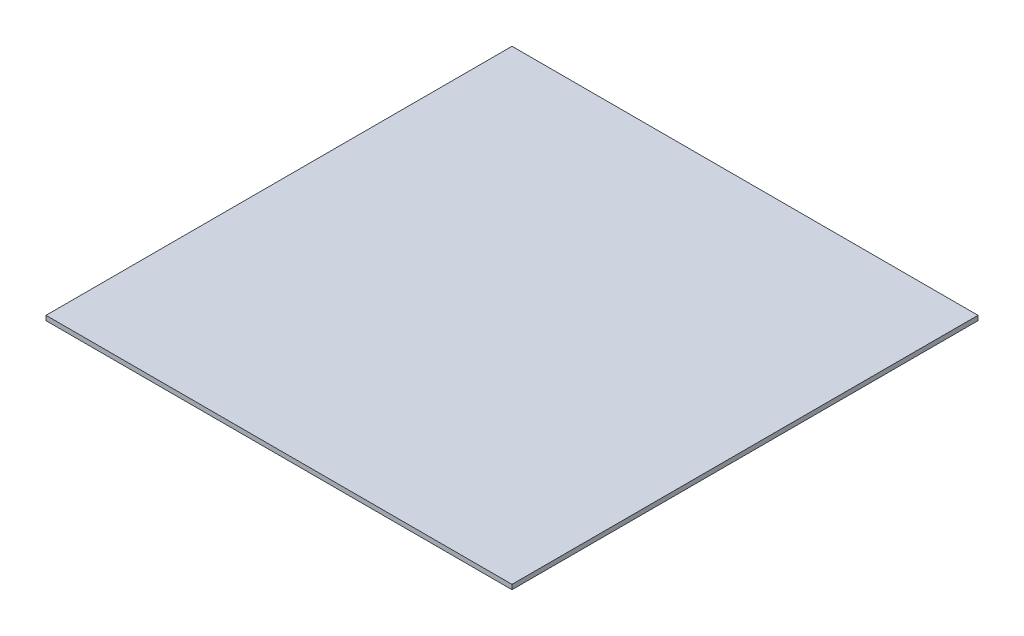
SolidWorks part; units mm, degrees
ref_plane "Front Plane" through (0, 0, 0) normal (0, 0, 1) x (1, 0, 0)
ref_plane "Top Plane" through (0, 0, 0) normal (0, 1, 0) x (1, 0, 0)
ref_plane "Right Plane" through (0, 0, 0) normal (1, 0, 0) x (0, 0, -1)
sketch "Sketch1" plane through (0, 0, 0) normal (0, 1, 0) x (1, 0, 0)
  line L1 (-150, 150) -> (150, 150)
  line L2 (-150, 150) -> (-150, -150)
  line L3 (-150, -150) -> (150, -150)
  line L4 (150, 150) -> (150, -150)
  line L5 (-150, 150) -> (150, -150) construction
  line L6 (-150, -150) -> (150, 150) construction
  point P0 (0, 0)
  dimension "D1" = 300
  dimension "D2" = 300
extrude "Boss-Extrude1" add sketch "Sketch1" along normal blind 3
